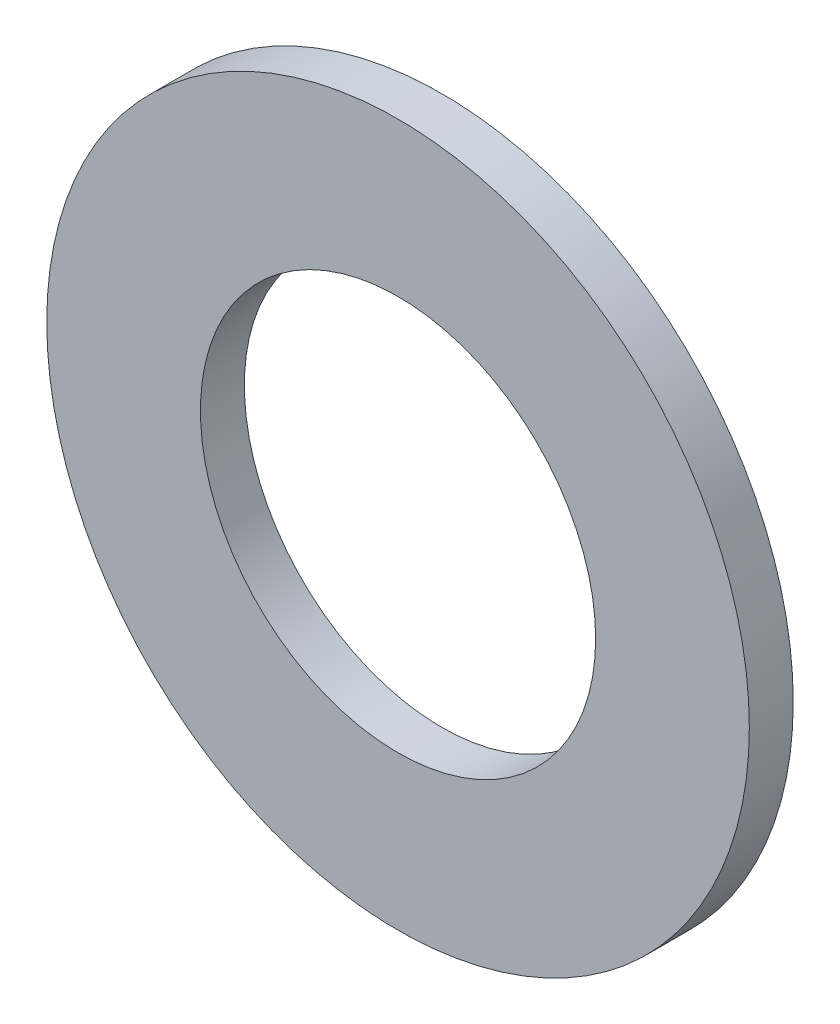
SolidWorks part; units mm, degrees
ref_plane "Front" through (0, 0, 0) normal (0, 0, 1) x (1, 0, 0)
ref_plane "Top" through (0, 0, 0) normal (0, 1, 0) x (1, 0, 0)
ref_plane "Right" through (0, 0, 0) normal (1, 0, 0) x (0, 0, -1)
sketch "Sketch1" plane through (0, 0, 0) normal (0, 0, 1) x (1, 0, 0)
  circle A0 centre (0, 0) radius 8
  dimension "D1" = 16
base flange "Base-Flange1" sketch "Sketch1" thickness 1 reverse thickness direction no parameters "D1"=1
sketch "Sketch6" plane through (0, 0, 0) normal (0, 0, 1) x (1, 0, 0)
  circle A0 centre (0, 0) radius 4.5
  dimension "D1" = 9
extrude "Cut-Extrude1" cut sketch "Sketch6" against normal through all normal cut yes
sketch "Bend-Lines1" plane through (0, 0, 0) normal (0, 1, 0) x (1, 0, 0)
sketch "Bounding-Box1" plane through (0, 0, 0) normal (0, 1, 0) x (1, 0, 0)
sheet metal parameters "Sheet-Metal(1)" thickness 1 parameters "D1"=1
flat pattern "Flat-Pattern(1)" [suppressed]
sketch "Bend-Lines2" plane through (0, 0, 0) normal (0, 1, 0) x (1, 0, 0)
sketch "Bounding-Box2" [suppressed] plane through (0, 0, 0) normal (0, 1, 0) x (1, 0, 0)
sheet metal parameters "Sheet-Metal(2)" thickness 1 parameters "D1"=1
flat pattern "Flat-Pattern(1)"
sketch "Bend-Lines2" plane through (0, 0, 0) normal (0, 1, 0) x (1, 0, 0)
sketch "Bounding-Box2" [suppressed] plane through (0, 0, 0) normal (0, 1, 0) x (1, 0, 0)
